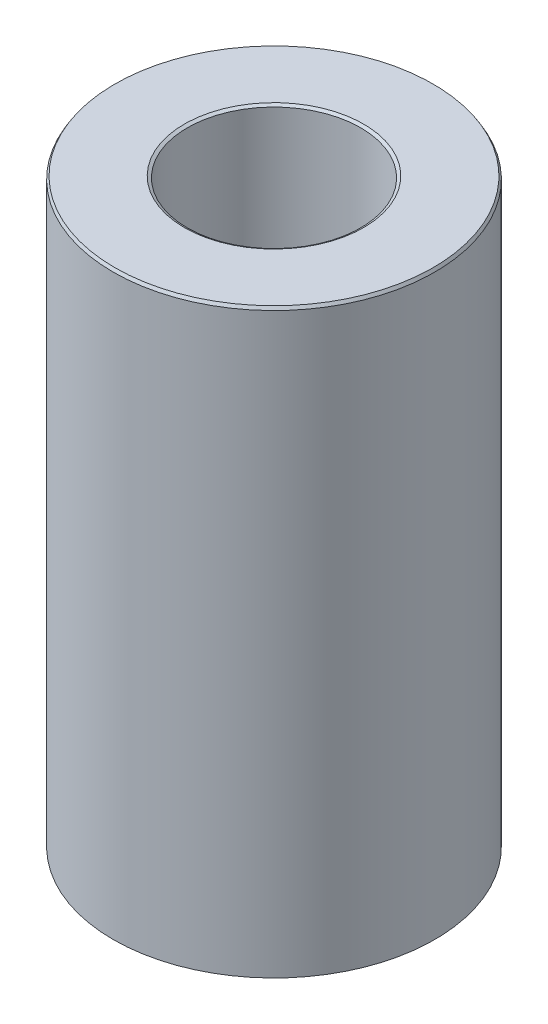
SolidWorks part; units mm, degrees
ref_plane "Front Plane" through (0, 0, 0) normal (0, 0, 1) x (1, 0, 0)
ref_plane "Top Plane" through (0, 0, 0) normal (0, 1, 0) x (1, 0, 0)
ref_plane "Right Plane" through (0, 0, 0) normal (1, 0, 0) x (0, 0, -1)
sketch "Sketch1" plane through (0, 0, 0) normal (0, 1, 0) x (1, 0, 0)
  circle A0 centre (0, 0) radius 47.5
  dimension "SLEEVE_OD" = 95
extrude "Boss-Extrude1" add sketch "Sketch1" along normal blind 172.1198
sketch "Sketch2" plane through (0, 0, 0) normal (0, 1, 0) x (1, 0, 0)
  circle A0 centre (0, 0) radius 25.6125
  dimension "BORE_D" = 51.225
extrude "Cut-Extrude1" cut sketch "Sketch2" along normal through all
chamfer "Chamfer1" distance 0.8761 angle 30 4 edges at (0, 172.1198, 25.6125) (0, 0, 25.6125) (0, 0, 47.5) (0, 172.1198, 47.5) first distance on face at (0, 172.1198, 25.6125) first distance on face at (0, 0, 25.6125) first distance on face at (0, 172.1198, 47.5)
